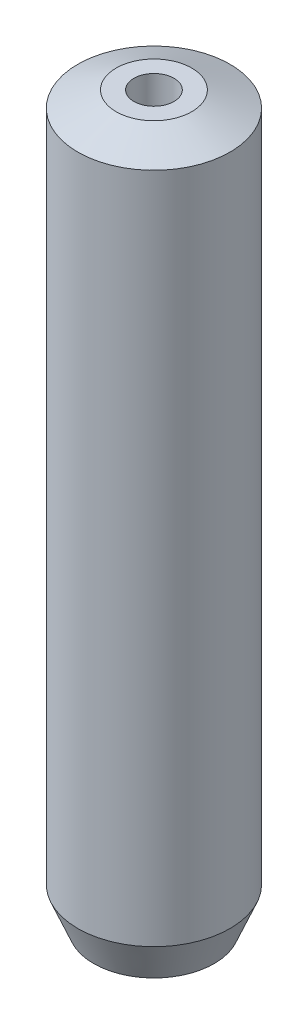
SolidWorks part; units mm, degrees
ref_plane "Front Plane" through (0, 0, 0) normal (0, 0, 1) x (1, 0, 0)
ref_plane "Top Plane" through (0, 0, 0) normal (0, 1, 0) x (1, 0, 0)
ref_plane "Right Plane" through (0, 0, 0) normal (1, 0, 0) x (0, 0, -1)
sketch "Sketch1" plane through (0, 0, 0) normal (0, 1, 0) x (1, 0, 0)
  circle A0 centre (0, 0) radius 5
  dimension "SHAFT_OD" = 10
extrude "Boss-Extrude1" add sketch "Sketch1" along normal blind 47.7139
sketch "Sketch2" plane through (0, 0, 0) normal (0, 1, 0) x (1, 0, 0)
  circle A0 centre (0, 0) radius 1.3194
  dimension "BORE_D" = 2.6388
extrude "Cut-Extrude1" cut sketch "Sketch2" along normal through all
chamfer "Chamfer1" distance 1.0396 angle 67.55 2 edges at (0, 47.7139, 5) (0, 0, 5) first distance on face at (0, 47.7139, 5) first distance on face at (0, 0, 1.3194)
